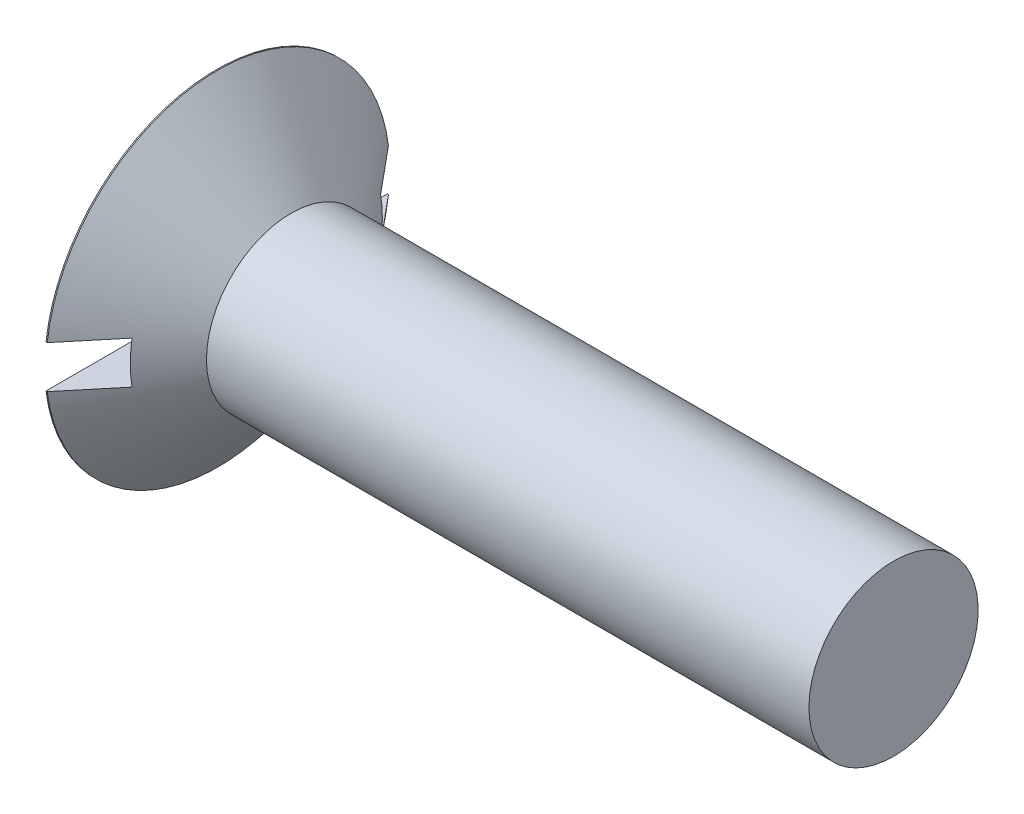
SolidWorks part; units mm, degrees
revolve "Base-Revolve" add sketch "BodySke" angle 360 about L5
sketch "BodySke" plane through (0, 0, 0) normal (0, 0, 1) x (1, 0, 0)
  line L0 (0, 0) -> (0, 9.6774)
  line L1 (0, 9.6774) -> (0.0669, 9.6774)
  line L2 (4.191, 4.7625) -> (38.1, 4.7625)
  line L3 (38.1, 4.7625) -> (38.1, 0)
  line L4 (38.1, 0) -> (0, 0)
  line L5 (-6.35, 0) -> (82.55, 0) construction
  line L6 (4.191, -4.7625) -> (38.1, -4.7625) construction
  line L7 (0.0669, -9.6774) -> (4.191, -4.7625) construction
  line L8 (0.0669, 9.6774) -> (4.191, 4.7625)
  line L9 (0, -9.6774) -> (0.0669, -9.6774) construction
  line L10 (5.7785, 6.35) -> (5.7785, -3.175) construction
  line L11 (6.35, 6.35) -> (6.35, -3.175) construction
  dimension "D6" = 0.0669
  dimension "Diameter" = 9.525
cosmetic thread "ThreadCosmetic" [suppressed] parameters "Thread_length"=31.75, "Thread_minor"=7.9248
extrude "Slot" cut sketch "Sketch2" against normal blind 2.2352
sketch "Sketch2" plane through (0, 0, 0) normal (-1, 0, 0) x (0, 0, 1)
  line L0 (-9.6774, -1.1938) -> (9.6774, -1.1938)
  line L1 (-9.6774, -1.1938) -> (-9.6774, 1.1938)
  line L2 (9.6774, 1.1938) -> (-9.6774, 1.1938)
  line L3 (9.6774, 1.1938) -> (9.6774, -1.1938)
  dimension "D1" = 1.1938
  dimension "D2" = 19.3548
  dimension "D3" = 9.6774
ref_plane "Plane1" through (0, 0, 0) normal (0, 0, 1) x (1, 0, 0)
ref_plane "Plane2" through (0, 0, 0) normal (0, 1, 0) x (1, 0, 0)
ref_plane "Plane3" through (0, 0, 0) normal (1, 0, 0) x (0, 0, -1)
sketch "Sketch3" plane through (0, 0, 0) normal (-1, 0, 0) x (0, 0, 1)
  line L0 (-1.0922, 6.6421) -> (1.0922, 6.6421)
  line L1 (1.0922, 6.6421) -> (1.0922, -6.6421)
  line L2 (1.0922, -6.6421) -> (-1.0922, -6.6421)
  line L3 (-1.0922, -6.6421) -> (-1.0922, 6.6421)
  dimension "Cross_dia" = 13.2842
  dimension "Cross_width" = 2.1844
  dimension "D1" = 6.6421
  dimension "D2" = 1.0922
ref_plane "Plane4" through (7.9756, 0, 0) normal (-1, 0, 0) x (0, 0, 1)
sketch "Sketch4" plane through (7.9756, 0, 0) normal (-1, 0, 0) x (0, 0, 1)
  line L0 (-0.5461, 0.5461) -> (0.5461, 0.5461)
  line L3 (0.5461, 0.5461) -> (0.5461, -0.5461)
  line L4 (0.5461, -0.5461) -> (-0.5461, -0.5461)
  line L5 (-0.5461, -0.5461) -> (-0.5461, 0.5461)
  dimension "D2" = 1.0922
  dimension "D1" = 1.0922
  dimension "D3" = 0.5461
  dimension "D4" = 0.5461
loft "Cross" cut profiles "Sketch3", "Sketch4"
pattern_circular "CirPattern1" count 2 every 90 about axis through (-6.35, 0, 0) along (1, 0, 0) of "Cross"
sketch "ThdSchSke" plane through (0, 0, 0) normal (0, 0, 1) x (1, 0, 0)
  line L0 (6.35, -3.9624) -> (5.7898, -4.7625)
  line L1 (6.35, -3.9624) -> (6.9103, -4.7625)
  line L2 (6.9103, -4.7625) -> (6.9103, -5.9531)
  line L3 (-3.175, 0) -> (5.1513, 0) construction
  line L5 (6.9103, -5.9531) -> (5.7898, -5.9531)
  line L6 (5.7898, -5.9531) -> (5.7898, -4.7625)
  line L7 (0, 9.6774) -> (0, 1.1938) construction
  dimension "Thread_minor" = 7.9248
  dimension "Diameter" = 9.525
  dimension "Start" = 6.35
revolve "ThreadSchematic" [suppressed] cut sketch "ThdSchSke" angle 360 about L3
pattern_linear "ThdSchPat" [suppressed]
equation "\"D1@Sketch3\" = \"Cross_dia@Sketch3\" / 2"
equation "\"D2@Sketch3\" = \"Cross_width@Sketch3\" / 2"
equation "\"D1@Sketch4\" = \"Cross_width@Sketch3\" *.5"
equation "\"D2@Sketch4\" = \"D1@Sketch4\""
equation "\"D4@Sketch4\" = \"D2@Sketch4\" / 2"
equation "\"D3@Sketch4\" = \"D1@Sketch4\" / 2"
equation "\"D1@Sketch2\" = \"Slot_width@Sketch2\" / 2"
equation "\"D2@Sketch2\" = \"Head_dia@BodySke\""
equation "\"D3@Sketch2\" = \"D2@Sketch2\" / 2"
equation "\"Thread_length@ThreadCosmetic\" = ((sgn( (\"Length@BodySke\" - \"Advance@BodySke\" - \"Head_ht@BodySke\" ) - \"Thread_nom@BodySke\" )-1)*( (\"Length@BodySke\" - \"Advance@BodySke\" - \"Head_ht@BodySke\" ) - \"Thread_nom@BodySke\" ))/-2+ \"Thread_nom@BodySke\""
equation "\"Thread_minor@ThdSchSke\" = \"Thread_minor@ThreadCosmetic\""
equation "\"Diameter@ThdSchSke\" = \"Diameter@BodySke\""
equation "\"Overcut@ThdSchSke\" = \"Diameter@BodySke\" * 1.25"
equation "\"Start@ThdSchSke\" = 0.000001 + \"Length@BodySke\" - \"Thread_length@ThreadCosmetic\"  '---Countersunk---"
equation "\"Num_threads@ThdSchPat\" = int( \"Thread_length@ThreadCosmetic\" / \"Advance@BodySke\" + 0.999 )  + 1"
equation "\"Advance@ThdSchPat\" = \"Thread_length@ThreadCosmetic\" /  (\"Num_threads@ThdSchPat\" - 1) 'relax it"
